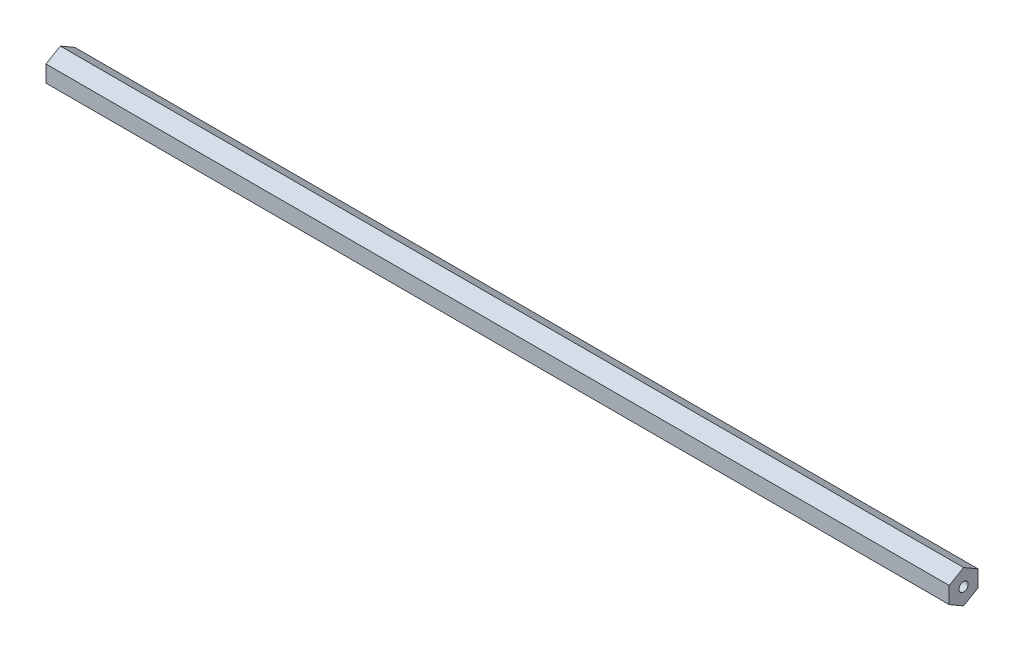
SolidWorks part; units mm, degrees
material "7075-T6 (SN)"
ref_plane "Front Plane" through (0, 0, 0) normal (0, 0, 1) x (1, 0, 0)
ref_plane "Top Plane" through (0, 0, 0) normal (0, 1, 0) x (1, 0, 0)
ref_plane "Right Plane" through (0, 0, 0) normal (1, 0, 0) x (0, 0, -1)
sketch "Sketch1" plane through (0, 0, 0) normal (1, 0, 0) x (0, 0, -1)
  line L1 (0, 7.3323) -> (-6.35, 3.6662)
  line L2 (-6.35, 3.6662) -> (-6.35, -3.6662)
  line L3 (-6.35, -3.6662) -> (0, -7.3323)
  line L4 (0, -7.3323) -> (6.35, -3.6662)
  line L5 (6.35, -3.6662) -> (6.35, 3.6662)
  line L6 (6.35, 3.6662) -> (0, 7.3323)
  circle A2 centre (0, 0) radius 6.35 construction
  dimension "D2" = 12.7
extrude "Boss-Extrude1" add sketch "Sketch1" along normal mid plane 398.526 contours L5 L6 L1 L2 L3 L4 region at (0, 0, 0)
hole_wizard "#10-32 Tapped Hole1" positions "3DSketch1" profile "Sketch2" tap size "#10-32" standard "ANSI Inch"
sketch3d "3DSketch1"
  point P0 (199.263, 0, 0)
  point P2 (-199.263, 0, 0)
sketch "Sketch2" plane through (199.263, 0, 0) normal (0, 1, 0) x (0, 0, -1)
  line L0 (0, 0) -> (0, 17.5608)
  line L1 (0, 17.5608) -> (2.0193, 16.3474)
  line L2 (2.0193, 16.3474) -> (2.0193, 0)
  line L5 (2.0193, 0) -> (0, 0)
  line L10 (0, 17.5608) -> (-2.0193, 16.3474) construction
  line L11 (0, -6.35) -> (0, 107.95) construction
  dimension "Tap Drill Dia." = 4.0386
  dimension "Tap Drill Depth" = 16.3474
  dimension "Drill Angle" = 118
cosmetic thread "Hole Thread1" parameters "D1"=13.97, "D2"=4.826
cosmetic thread "Hole Thread2" parameters "D1"=13.97, "D2"=4.826
